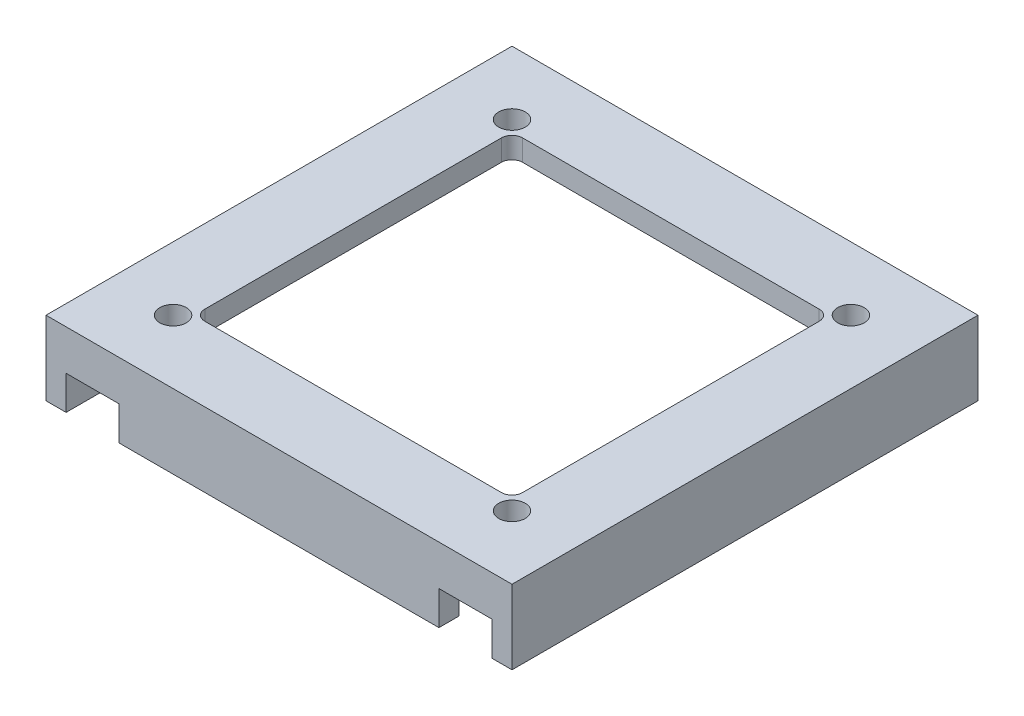
SolidWorks part; units mm, degrees
ref_plane "Front Plane" through (0, 0, 0) normal (0, 0, 1) x (1, 0, 0)
ref_plane "Top Plane" through (0, 0, 0) normal (0, 1, 0) x (1, 0, 0)
ref_plane "Right Plane" through (0, 0, 0) normal (1, 0, 0) x (0, 0, -1)
sketch "Sketch1" plane through (0, 0, 0) normal (0, 1, 0) x (1, 0, 0)
  line L0 (20.1, -20.1) -> (20.1, 21.1)
  line L1 (-20.1, -20.1) -> (20.1, -20.1)
  line L3 (-18.1, 20.1) -> (18.1, 20.1)
  line L5 (-20.1, 21.1) -> (-20.1, -20.1)
  line L6 (-22, 22) -> (22, 22)
  line L7 (-22, -22) -> (22, -22)
  line L8 (-22, -22) -> (-22, 22)
  line L10 (22, -22) -> (22, 22)
  line L15 (-20.1, 21.1) -> (-18.1, 21.1)
  line L16 (-18.1, 20.1) -> (-18.1, 21.1)
  line L19 (20.1, 21.1) -> (18.1, 21.1)
  line L20 (18.1, 20.1) -> (18.1, 21.1)
  point P0 (0, 0)
  point P15 (0, 0)
  dimension "D14" = 2
  dimension "D21" = 22
  dimension "D13" = 22
  dimension "D2" = 40.2
  dimension "D12" = 22
  dimension "D15" = 1
  dimension "D16" = 2
  dimension "D17" = 1
  dimension "D18" = 20.1
  dimension "D19" = 40.2
  dimension "D20" = 20.1
  dimension "D22" = 22
extrude "Boss-Extrude1" add sketch "Sketch1" along normal blind 5
sketch "Sketch2" plane through (0, 5, 0) normal (0, 1, 0) x (1, 0, 0)
  line L12 (-18, -18) -> (18, -18)
  line L13 (18, -18) -> (18, 18)
  line L14 (-18, 18) -> (-18, -18)
  line L15 (18, 18) -> (-18, 18)
  line L54 (-20.1, 21.1) -> (-20.1, -20.1)
  line L55 (-20.1, -20.1) -> (20.1, -20.1)
  line L56 (20.1, -20.1) -> (20.1, 21.1)
  line L57 (20.1, 21.1) -> (18.1, 21.1)
  line L58 (18.1, 21.1) -> (18.1, 20.1)
  line L59 (18.1, 20.1) -> (-18.1, 20.1)
  line L60 (-18.1, 20.1) -> (-18.1, 21.1)
  line L61 (-18.1, 21.1) -> (-20.1, 21.1)
  line L62 (-20.1, 21.1) -> (-20.1, -20.1)
  line L63 (-20.1, -20.1) -> (20.1, -20.1)
  line L64 (20.1, -20.1) -> (20.1, 21.1)
  line L65 (20.1, 21.1) -> (18.1, 21.1)
  line L66 (18.1, 21.1) -> (18.1, 20.1)
  line L67 (18.1, 20.1) -> (-18.1, 20.1)
  line L68 (-18.1, 20.1) -> (-18.1, 21.1)
  line L69 (-18.1, 21.1) -> (-20.1, 21.1)
  dimension "D1" = 36
  dimension "D3" = 36
  dimension "D4" = 18
  dimension "D5" = 18
  dimension "D6" = 36
  dimension "D7" = 36
  dimension "D2" = 0
extrude "Boss-Extrude2" add sketch "Sketch2" against normal blind 1.8
sketch "Sketch3" plane through (0, 0, 22) normal (0, 0, 1) x (1, 0, 0)
  line L0 (-22, 0) -> (22, 0) construction
  line L1 (-20.1, 0) -> (-15.1, 0)
  line L3 (-20.1, 3.2) -> (-15.1, 3.2)
  line L4 (-15.1, 0) -> (-15.1, 3.2)
  line L5 (20.1, 0) -> (20.1, 3.2)
  line L6 (20.1, 0) -> (15.1, 0)
  line L8 (20.1, 3.2) -> (15.1, 3.2)
  line L9 (15.1, 0) -> (15.1, 3.2)
  line L10 (-20.1, 0) -> (-20.1, 3.2)
  dimension "D1" = 5
  dimension "D2" = 5
  dimension "D3" = 0
  dimension "D4" = 0
  dimension "D5" = 3.2
  dimension "D6" = 3.2
extrude "Cut-Extrude1" cut sketch "Sketch3" against normal up to next
sketch "Sketch4" plane through (0, 5, 0) normal (0, 1, 0) x (1, 0, 0)
  line L1 (15, -15) -> (-15, -15)
  line L2 (15, -15) -> (15, 15)
  line L3 (15, 15) -> (-15, 15)
  line L4 (-15, -15) -> (-15, 15)
  line L5 (15, -15) -> (-15, 15) construction
  line L6 (15, 15) -> (-15, -15) construction
  line L7 (22, -22) -> (-22, -22)
  line L8 (22, -22) -> (22, 22)
  line L9 (22, 22) -> (-22, 22)
  line L10 (-22, -22) -> (-22, 22)
  line L11 (22, -22) -> (-22, 22) construction
  line L12 (22, 22) -> (-22, -22) construction
  point P0 (0, 0)
  point P5 (0, 0)
  dimension "D1" = 30
  dimension "D2" = 30
extrude "Boss-Extrude3" add sketch "Sketch4" along normal blind 2
fillet "Fillet1" radius 1 12 edges at (-18, 4.1, 18) (18, 4.1, 18) (18, 4.1, -18) (-18, 4.1, -18) (-20.1, 1.6, -21.1) (-18.1, 1.6, -21.1) (18.1, 1.6, -21.1) (20.1, 1.6, -21.1) (-15, 6, -15) (-15, 6, 15) (15, 6, -15) (15, 6, 15)
hole_wizard "Tap Drill for M3 Tap1" positions "Sketch6" profile "Sketch7" hole size "M3" standard "ISO" end condition up to next
sketch "Sketch6" plane through (0, 7, 0) normal (0, 1, 0) x (1, 0, 0)
  point P0 (-16, 16)
  point P2 (16, 16)
  point P4 (16, -16)
  point P6 (-16, -16)
  dimension "D1" = 16
  dimension "D2" = 16
  dimension "D3" = 16
  dimension "D4" = 16
  dimension "D5" = 16
  dimension "D6" = 16
  dimension "D7" = 16
  dimension "D8" = 16
sketch "Sketch7" plane through (-16, 7, -16) normal (1, 0, 0) x (0, 0, 1)
  line L0 (0, 0) -> (0, 2)
  line L1 (0, 2) -> (1.25, 2)
  line L2 (1.25, 2) -> (1.25, 0)
  line L5 (1.25, 0) -> (0, 0)
  line L11 (0, -6.35) -> (0, 107.95) construction
  dimension "Thru Hole Dia." = 2.5
  dimension "Thru Hole Depth" = 2
